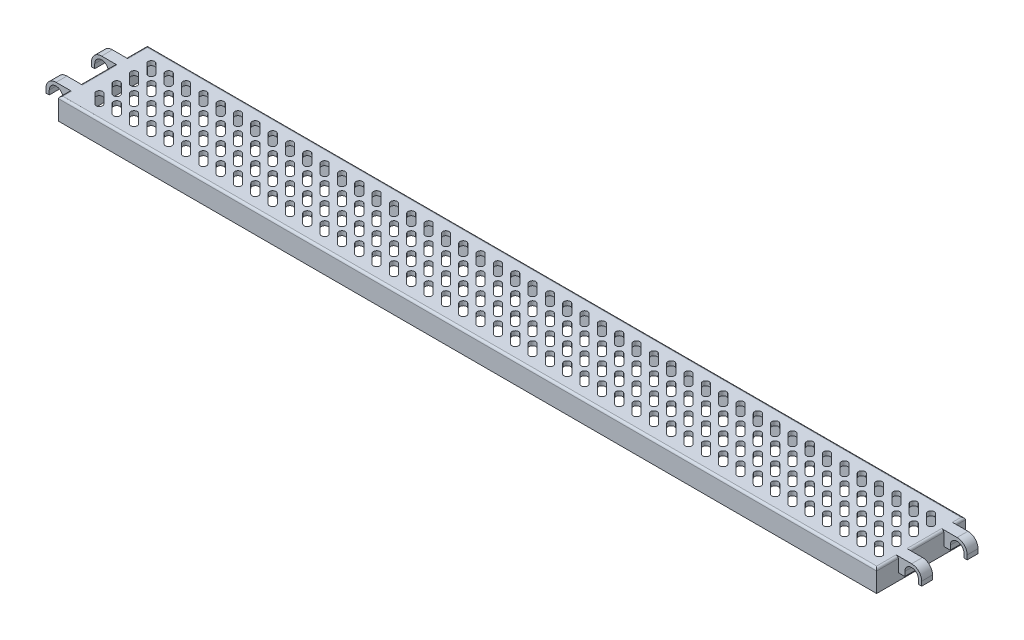
SolidWorks part; units mm, degrees
ref_plane "Ebene vorne" through (0, 0, 0) normal (0, 0, 1) x (1, 0, 0)
ref_plane "Ebene oben" through (0, 0, 0) normal (0, 1, 0) x (1, 0, 0)
ref_plane "Ebene rechts" through (0, 0, 0) normal (1, 0, 0) x (0, 0, -1)
sketch "Skizze1" plane through (0, 0, 0) normal (0, 0, 1) x (1, 0, 0)
  line L0 (-195, 0) -> (195, 0) construction
  line L1 (-198.15, 0) -> (-198.15, -2)
  line L2 (-191.85, 0) -> (-191.85, -2)
  line L3 (-188.85, -5.35) -> (188.85, -5.35)
  line L4 (-198.15, -2) -> (-199.65, -2)
  line L5 (-199.65, -2) -> (-199.65, 0)
  line L6 (-195, 4.65) -> (195, 4.65)
  line L7 (0, 4.65) -> (0, -5.35) construction
  line L8 (-191.85, -2) -> (-188.85, -2)
  line L9 (-188.85, -2) -> (-188.85, -5.35)
  line L10 (188.85, -2) -> (188.85, -5.35)
  line L11 (191.85, -2) -> (188.85, -2)
  line L12 (199.65, -2) -> (199.65, 0)
  line L13 (198.15, -2) -> (199.65, -2)
  line L14 (191.85, 0) -> (191.85, -2)
  line L15 (198.15, 0) -> (198.15, -2)
  arc A0 (-198.15, 0) -> (-191.85, 0) centre (-195, 0) cw
  arc A1 (-199.65, 0) -> (-195, 4.65) centre (-195, 0) cw
  arc A2 (199.65, 0) -> (195, 4.65) centre (195, 0) ccw
  arc A3 (198.15, 0) -> (191.85, 0) centre (195, 0) ccw
  point P3 (0, 0)
  dimension "D2" = 3.15
  dimension "D1" = 390
  dimension "D3" = 1.5
  dimension "D4" = 2
  dimension "D5" = 10
  dimension "D6" = 3
extrude "Aufsatz-Linear austragen2" add sketch "Skizze1" along normal mid plane 41
sketch "Skizze3" plane through (0, -5.35, 0) normal (0, -1, 0) x (1, 0, 0)
  line L0 (-188.85, 20.5) -> (-188.85, -20.5) construction
  line L1 (-199.65, 20.5) -> (-188.85, 20.5)
  line L2 (-199.65, 20.5) -> (-199.65, 15.5)
  line L3 (-199.65, 15.5) -> (-188.85, 15.5)
  line L4 (-188.85, 20.5) -> (-188.85, 15.5)
  line L5 (-199.65, 20.5) -> (-199.65, -20.5) construction
  line L6 (-199.65, 10.5) -> (-188.85, 10.5)
  line L7 (-199.65, 10.5) -> (-199.65, -5.5)
  line L8 (-199.65, -5.5) -> (-188.85, -5.5)
  line L9 (-188.85, 10.5) -> (-188.85, -5.5)
  line L10 (-188.85, 20.5) -> (-188.85, -20.5) construction
  line L11 (199.65, 20.5) -> (199.65, -20.5) construction
  line L12 (-199.65, -20.5) -> (-188.85, -20.5)
  line L13 (-199.65, -20.5) -> (-199.65, -10.5)
  line L14 (-199.65, -10.5) -> (-188.85, -10.5)
  line L15 (-188.85, -20.5) -> (-188.85, -10.5)
  line L16 (188.85, 20.5) -> (199.65, 20.5)
  line L17 (188.85, 20.5) -> (188.85, 10.5)
  line L18 (188.85, 10.5) -> (199.65, 10.5)
  line L19 (199.65, 20.5) -> (199.65, 10.5)
  line L20 (188.85, 20.5) -> (188.85, -20.5) construction
  line L21 (188.85, 5.5) -> (199.65, 5.5)
  line L22 (188.85, 5.5) -> (188.85, -10.5)
  line L23 (188.85, -10.5) -> (199.65, -10.5)
  line L24 (199.65, 5.5) -> (199.65, -10.5)
  line L26 (188.85, -15.5) -> (199.65, -15.5)
  line L27 (188.85, -15.5) -> (188.85, -20.5)
  line L28 (188.85, -20.5) -> (199.65, -20.5)
  line L29 (199.65, -15.5) -> (199.65, -20.5)
  dimension "D1" = 5
  dimension "D2" = 5
  dimension "D3" = 5
  dimension "D4" = 10
  dimension "D5" = 5
  dimension "D6" = 5
extrude "Schnitt-Linear austragen1" cut sketch "Skizze3" against normal through all
sketch "Skizze4" plane through (0, -5.35, 0) normal (0, -1, 0) x (1, 0, 0)
  line L8 (-185.85, -17.5) -> (185.85, -17.5)
  line L9 (185.85, -17.5) -> (185.85, 17.5)
  line L10 (185.85, 17.5) -> (-185.85, 17.5)
  line L11 (-185.85, 17.5) -> (-185.85, -17.5)
  line L12 (-185.85, -17.5) -> (185.85, -17.5)
  line L13 (185.85, -17.5) -> (185.85, 17.5)
  line L14 (185.85, 17.5) -> (-185.85, 17.5)
  line L15 (-185.85, 17.5) -> (-185.85, -17.5)
  dimension "D1" = 3
extrude "Schnitt-Linear austragen2" cut sketch "Skizze4" against normal offset from surface (8 mm away) 2 up to face at (0, 4.65, 0)
sketch "Skizze5" plane through (0, 2.65, 0) normal (0, -1, 0) x (1, 0, 0)
  line L0 (-185.85, -17.5) -> (185.85, -17.5) construction
  line L1 (-180.6, -14.1) -> (-176.3574, -9.8574) construction
  line L2 (-181.6607, -13.0393) -> (-177.418, -8.7967)
  line L3 (-179.5393, -15.1607) -> (-175.2967, -10.918)
  line L4 (185.85, -17.5) -> (-185.85, -17.5) construction
  line L5 (-185.85, -17.5) -> (-185.85, 17.5) construction
  arc A0 (-181.6607, -13.0393) -> (-179.5393, -15.1607) centre (-180.6, -14.1) ccw
  arc A1 (-175.2967, -10.918) -> (-177.418, -8.7967) centre (-176.3574, -9.8574) ccw
  point P4 (-178.4787, -11.9787)
  dimension "D3" = 9
  dimension "D4" = 1.9
  dimension "D5" = 3.75
  dimension "D1" = 45
  dimension "D2" = 3
extrude "Schnitt-Linear austragen3" cut sketch "Skizze5" against normal through all
pattern_linear "Lineares Muster1" count 46 spacing 8 along (1, 0, 0) count 4 spacing 8 along (0, 0, 1) of "Schnitt-Linear austragen3"
fillet "Verrundung1" radius 1 8 edges at (-188.85, 4.65, 18) (-188.85, 4.65, 2.5) (-188.85, 4.65, -15.5) (0, 4.65, 20.5) (188.85, 4.65, 15.5) (188.85, 4.65, -2.5) (0, 4.65, -20.5) (188.85, 4.65, -18)
